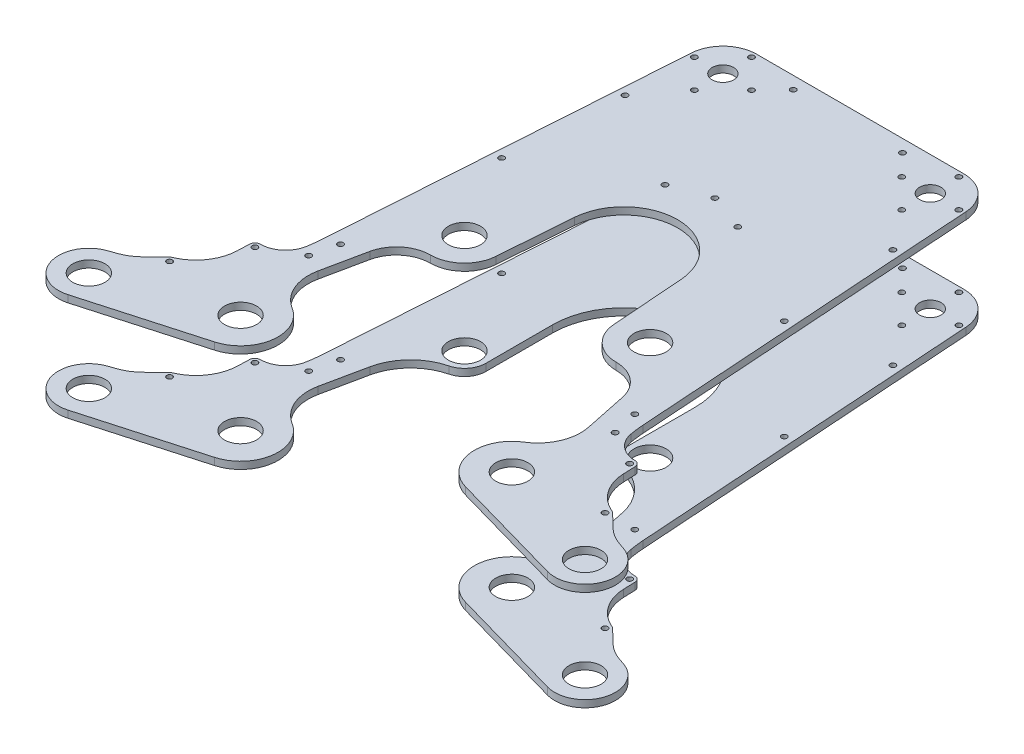
SolidWorks part; units mm, degrees
ref_plane "Alzado" through (0, 0, 0) normal (0, 0, 1) x (1, 0, 0)
ref_plane "Planta" through (0, 0, 0) normal (0, 1, 0) x (1, 0, 0)
ref_plane "Vista lateral" through (0, 0, 0) normal (1, 0, 0) x (0, 0, -1)
sketch "llantas" plane through (0, 0, 0) normal (0, 1, 0) x (1, 0, 0)
  line L0 (0, 221.5734) -> (0, 0) construction
  line L1 (-215.9, 0) -> (0, 0) construction
  circle A0 centre (-93.6625, 101.6) radius 50.8
  circle A1 centre (-215.9, 0) radius 38.1
  circle A2 centre (215.9, 0) radius 38.1
  circle A3 centre (93.6625, 101.6) radius 50.8
  dimension "D1" = 101.6
  dimension "D2" = 42.8625
  dimension "D3" = 177.8
  dimension "D4" = 76.2
  dimension "D5" = 101.6
sketch "cono" plane through (0, 0, 0) normal (1, 0, 0) x (0, 0, -1)
  line L0 (-76.2, 23.114) -> (-22.987, 324.358)
  line L1 (-22.987, 324.358) -> (22.987, 324.358)
  line L2 (0, 324.358) -> (0, 23.114) construction
  line L3 (76.2, 23.114) -> (-76.2, 23.114) construction
  line L4 (-76.2, 23.114) -> (-106.426, 23.114)
  line L5 (-106.426, 23.114) -> (-106.426, 0)
  line L6 (-106.426, 0) -> (106.426, 0)
  line L7 (0, 0) -> (0, 23.114)
  line L8 (-76.2, 23.114) -> (76.2, 23.114)
  line L9 (-80.283, 0) -> (80.283, 0)
  line L10 (221.5734, 0) -> (0, 0) construction
  line L11 (106.426, 23.114) -> (106.426, 0)
  line L12 (76.2, 23.114) -> (106.426, 23.114)
  line L13 (76.2, 23.114) -> (22.987, 324.358)
  line L14 (0, 220.8278) -> (41.275, 220.8278) construction
  dimension "D1" = 324.358
  dimension "D2" = 23.114
  dimension "D3" = 22.987
  dimension "D4" = 152.4
  dimension "D5" = 212.852
  dimension "D6" = 41.275
  dimension "D7" = 220.8278
sketch "Croquis4" plane through (0, 0, 0) normal (0, 1, 0) x (1, 0, 0)
  line L11 (0, 293.4478) -> (0, -300.8756) construction
  circle A36 centre (0, 179.087) radius 32.258
  dimension "D4" = 64.516
ref_plane "Plano1" through (0, 184.15, 0) normal (0, 1, 0) x (1, 0, 0)
sketch "Croquis11" plane through (0, 184.15, 0) normal (0, 1, 0) x (1, 0, 0)
  line L0 (0, -106.426) -> (0, 106.426) construction
  line L1 (-101.7784, 180.6897) -> (-111.1757, -58.1023) construction
  line L2 (0, 0) -> (0, -47.7539) construction
  line L3 (-82.7561, 181.459) -> (-54.1087, -55.7947) construction
  line L4 (-102.0644, -224.6803) -> (-63.9644, -63.6256) construction
  line L5 (-139.2356, -215.8869) -> (-101.1356, -54.8321) construction
  line L6 (0, 0) -> (-82.55, -59.2289) construction
  line L7 (0, 0) -> (0, -106.426) construction
  line L14 (-126.947, -202.253) -> (-226.9506, -237.178) construction
  line L15 (-114.353, -238.3143) -> (-214.3566, -273.2393) construction
  line L16 (0, 293.4478) -> (0, -300.8756) construction
  line L17 (-220.6536, -283.7836) -> (-120.65, -283.7836) construction
  circle A0 centre (0, 0) radius 47.7539 construction
  circle A1 centre (-82.55, -59.2289) radius 50.8
  circle A2 centre (-92.2365, 180.3142) radius 30
  arc A3 (-82.7561, 181.459) -> (-101.7784, 180.6897) centre (-92.2365, 180.3142) ccw construction
  arc A4 (-111.1757, -58.1023) -> (-54.1087, -55.7947) centre (-82.55, -59.2289) ccw construction
  arc A6 (-139.2356, -215.8869) -> (-102.0644, -224.6803) centre (-120.65, -220.2836) ccw construction
  arc A7 (-63.9644, -63.6256) -> (-101.1356, -54.8321) centre (-82.55, -59.2289) ccw construction
  circle A12 centre (-120.65, -220.2836) radius 50.8
  circle A13 centre (-220.6536, -255.2086) radius 28.575
  arc A14 (-226.9506, -237.178) -> (-214.3566, -273.2393) centre (-220.6536, -255.2086) ccw construction
  arc A15 (-114.353, -238.3143) -> (-139.2356, -215.8869) centre (-120.65, -220.2836) ccw construction
  dimension "D1" = 101.6
  dimension "D4" = 60
  dimension "D5" = 19.0986
  dimension "D6" = 57.2958
  dimension "D10" = 38.1972
  dimension "D17" = 101.6
  dimension "D13" = 57.15
  dimension "D14" = 38.1972
  dimension "D2" = 101.6
  dimension "D3" = 165.1
  dimension "D8" = 69.85
  dimension "D9" = 12.7
  dimension "D12" = 239.5431
sketch "Croquis40" plane through (0, 184.15, 0) normal (0, 1, 0) x (1, 0, 0)
  line L0 (-117.475, -110.0289) -> (117.475, -110.0289) construction
  line L1 (-117.475, -110.0289) -> (-117.475, -344.9789) construction
  line L2 (117.475, -110.0289) -> (117.475, -344.9789) construction
  line L3 (-117.475, -344.9789) -> (117.475, -344.9789) construction
  line L4 (0, 0) -> (0, -110.0289)
  circle A1 centre (-82.55, -59.2289) radius 50.8 construction
  dimension "D1" = 234.95
ref_plane "Plano2" through (0, 95.25, 0) normal (0, 1, 0) x (1, 0, 0)
sketch "Croquis12" plane through (0, 95.25, 0) normal (0, 1, 0) x (1, 0, 0)
  line L0 (0, 0) -> (0, -63.4576) construction
  circle A0 centre (0, 0) radius 63.4576 construction
  circle A1 centre (-82.55, -59.2289) radius 50.8
  circle A2 centre (-82.55, -59.2289) radius 50.8 construction
sketch "Croquis42" plane through (0, 184.15, 0) normal (0, 1, 0) x (1, 0, 0)
  line L10 (142.9479, -125.9298) -> (122.1686, 182.3319)
  line L11 (-47.6217, 3.5515) -> (-52.471, -61.4721)
  line L12 (-112.3836, -113.6275) -> (-120.3575, -151.7275)
  line L13 (-120.65, -220.2836) -> (-220.6536, -255.2086) construction
  line L14 (-111.5648, -252.3593) -> (-213.299, -281.1746)
  line L15 (0, 226.6032) -> (0, -226.6032) construction
  line L17 (229.5516, -229.7302) -> (219.3033, -226.1511)
  line L18 (-229.5516, -229.7302) -> (-219.3033, -226.1511)
  line L19 (-142.9479, -125.9298) -> (-122.1686, 182.3319)
  line L20 (-126.947, -202.253) -> (-226.9506, -237.178) construction
  line L21 (-92.2365, 210.3142) -> (92.2365, 210.3142)
  line L22 (111.5648, -252.3593) -> (213.299, -281.1746)
  line L23 (112.3836, -113.6275) -> (120.3575, -151.7275)
  line L24 (47.6217, 3.5515) -> (52.471, -61.4721)
  circle A11 centre (-220.6536, -255.2086) radius 14.2875
  circle A17 centre (-120.65, -220.2836) radius 14.2875
  circle A18 centre (-82.55, -59.2289) radius 14.2875
  arc A20 (47.6217, 3.5515) -> (-47.6217, 3.5515) centre (0, 0) ccw
  circle A21 centre (92.2365, 180.3142) radius 25.4 construction
  circle A22 centre (0, 0) radius 47.7539 construction
  arc A23 (-82.55, -89.3914) -> (-52.471, -61.4721) centre (-82.55, -59.2289) ccw
  arc A24 (-82.55, -89.3914) -> (-112.3836, -113.6275) centre (-82.55, -119.8714) ccw
  arc A25 (-111.5648, -252.3593) -> (-103.1106, -191.933) centre (-120.65, -220.2836) ccw
  arc A26 (-120.3575, -151.7275) -> (-103.1106, -191.933) centre (-83.0655, -159.5323) ccw
  arc A28 (-229.5516, -229.7302) -> (-213.299, -281.1746) centre (-220.6536, -255.2086) ccw
  circle A29 centre (120.65, -220.2836) radius 33.3375 construction
  circle A30 centre (117.6365, 180.3142) radius 2.4892
  circle A31 centre (-92.2365, 180.3142) radius 30 construction
  arc A32 (-92.2365, 210.3142) -> (-122.1686, 182.3319) centre (-92.2365, 180.3142) ccw
  circle A33 centre (-120.65, -220.2836) radius 33.3375 construction
  circle A34 centre (-92.2365, 180.3142) radius 25.4 construction
  circle A35 centre (-92.2365, 205.7142) radius 2.4892
  circle A36 centre (-66.8365, 180.3142) radius 2.4892
  circle A37 centre (-92.2365, 154.9142) radius 2.4892
  circle A38 centre (-117.6365, 180.3142) radius 2.4892
  circle A39 centre (92.2365, 154.9142) radius 2.4892
  circle A40 centre (66.8365, 180.3142) radius 2.4892
  circle A41 centre (92.2365, 205.7142) radius 2.4892
  arc A42 (92.2365, 210.3142) -> (122.1686, 182.3319) centre (92.2365, 180.3142) cw
  arc A43 (229.5516, -229.7302) -> (213.299, -281.1746) centre (220.6536, -255.2086) cw
  arc A44 (120.3575, -151.7275) -> (103.1106, -191.933) centre (83.0655, -159.5323) cw
  arc A45 (111.5648, -252.3593) -> (103.1106, -191.933) centre (120.65, -220.2836) cw
  arc A46 (82.55, -89.3914) -> (112.3836, -113.6275) centre (82.55, -119.8714) cw
  arc A47 (82.55, -89.3914) -> (52.471, -61.4721) centre (82.55, -59.2289) cw
  circle A48 centre (82.55, -59.2289) radius 14.2875
  circle A49 centre (120.65, -220.2836) radius 14.2875
  circle A50 centre (220.6536, -255.2086) radius 14.2875
  arc A52 (142.9479, -125.9298) -> (219.3033, -226.1511) centre (256.9891, -118.2425) ccw
  arc A53 (-219.3033, -226.1511) -> (-142.9479, -125.9298) centre (-256.9891, -118.2425) ccw
  circle A54 centre (-92.2365, 180.3142) radius 9.5631
  circle A55 centre (92.2365, 180.3142) radius 9.5631
  point P18 (-170.6518, -237.7461)
  point P52 (-92.2365, 180.3142)
  point P66 (148.0256, -201.2583)
  point P83 (0, 210.3142)
  point P85 (92.2365, 180.3142)
  point P86 (170.6518, -237.7461)
  point P90 (-148.0256, -201.2583)
  dimension "D1" = 28.575
  dimension "D2" = 19.05
  dimension "D3" = 12.7
  dimension "D4" = 15.875
  dimension "D5" = 38.1
  dimension "D7" = 30.48
  dimension "D8" = 50.8
  dimension "D9" = 4.9784
  dimension "D11" = 114.3
  dimension "D12" = 19.1262
  dimension "D6" = 38.1
  dimension "D10" = 4
extrude "4400-23-P-0501" add sketch "Croquis42" along normal blind 6.35
sketch "Croquis44" plane through (0, 95.25, 0) normal (0, 1, 0) x (1, 0, 0)
  line L0 (92.2365, 210.3142) -> (-92.2365, 210.3142) construction
  line L1 (-122.1686, 182.3319) -> (-142.9479, -125.9298) construction
  line L2 (92.2365, 210.3142) -> (-92.2365, 210.3142)
  line L3 (-122.1686, 182.3319) -> (-142.9479, -125.9298)
  line L4 (142.9479, -125.9298) -> (122.1686, 182.3319) construction
  line L5 (229.5516, -229.7302) -> (219.3033, -226.1511) construction
  line L6 (111.5648, -252.3593) -> (213.299, -281.1746) construction
  line L7 (112.3836, -113.6275) -> (120.3575, -151.7275) construction
  line L10 (-120.3575, -151.7275) -> (-112.3836, -113.6275) construction
  line L11 (-213.299, -281.1746) -> (-111.5648, -252.3593) construction
  line L12 (-219.3033, -226.1511) -> (-229.5516, -229.7302) construction
  line L13 (142.9479, -125.9298) -> (122.1686, 182.3319)
  line L14 (229.5516, -229.7302) -> (219.3033, -226.1511)
  line L15 (111.5648, -252.3593) -> (213.299, -281.1746)
  line L16 (112.3836, -113.6275) -> (120.3575, -151.7275)
  line L19 (-120.3575, -151.7275) -> (-112.3836, -113.6275)
  line L20 (-213.299, -281.1746) -> (-111.5648, -252.3593)
  line L21 (-219.3033, -226.1511) -> (-229.5516, -229.7302)
  line L22 (-63.4576, -59.2289) -> (-63.4576, 0)
  line L23 (63.4576, -59.2289) -> (63.4576, 0)
  line L24 (0, 0) -> (0, -147.841) construction
  arc A0 (-219.3033, -226.1511) -> (-142.9479, -125.9298) centre (-256.9891, -118.2425) ccw construction
  arc A1 (-92.2365, 210.3142) -> (-122.1686, 182.3319) centre (-92.2365, 180.3142) ccw construction
  arc A2 (-219.3033, -226.1511) -> (-142.9479, -125.9298) centre (-256.9891, -118.2425) ccw
  arc A3 (-92.2365, 210.3142) -> (-122.1686, 182.3319) centre (-92.2365, 180.3142) ccw
  arc A4 (122.1686, 182.3319) -> (92.2365, 210.3142) centre (92.2365, 180.3142) ccw construction
  arc A5 (142.9479, -125.9298) -> (219.3033, -226.1511) centre (256.9891, -118.2425) ccw construction
  arc A6 (213.299, -281.1746) -> (229.5516, -229.7302) centre (220.6536, -255.2086) ccw construction
  arc A7 (103.1106, -191.933) -> (111.5648, -252.3593) centre (120.65, -220.2836) ccw construction
  arc A8 (103.1106, -191.933) -> (120.3575, -151.7275) centre (83.0655, -159.5323) ccw construction
  arc A14 (-120.3575, -151.7275) -> (-103.1106, -191.933) centre (-83.0655, -159.5323) ccw construction
  arc A15 (-111.5648, -252.3593) -> (-103.1106, -191.933) centre (-120.65, -220.2836) ccw construction
  arc A16 (-229.5516, -229.7302) -> (-213.299, -281.1746) centre (-220.6536, -255.2086) ccw construction
  arc A17 (122.1686, 182.3319) -> (92.2365, 210.3142) centre (92.2365, 180.3142) ccw
  arc A18 (142.9479, -125.9298) -> (219.3033, -226.1511) centre (256.9891, -118.2425) ccw
  arc A19 (213.299, -281.1746) -> (229.5516, -229.7302) centre (220.6536, -255.2086) ccw
  arc A20 (103.1106, -191.933) -> (111.5648, -252.3593) centre (120.65, -220.2836) ccw
  arc A21 (103.1106, -191.933) -> (120.3575, -151.7275) centre (83.0655, -159.5323) ccw
  arc A27 (-120.3575, -151.7275) -> (-103.1106, -191.933) centre (-83.0655, -159.5323) ccw
  arc A28 (-111.5648, -252.3593) -> (-103.1106, -191.933) centre (-120.65, -220.2836) ccw
  arc A29 (-229.5516, -229.7302) -> (-213.299, -281.1746) centre (-220.6536, -255.2086) ccw
  circle A30 centre (92.2365, 180.3142) radius 9.5631 construction
  circle A31 centre (92.2365, 154.9142) radius 2.4892 construction
  circle A32 centre (117.6365, 180.3142) radius 2.4892 construction
  circle A33 centre (92.2365, 205.7142) radius 2.4892 construction
  circle A34 centre (66.8365, 180.3142) radius 2.4892 construction
  circle A35 centre (-92.2365, 180.3142) radius 9.5631 construction
  circle A36 centre (-66.8365, 180.3142) radius 2.4892 construction
  circle A37 centre (-92.2365, 205.7142) radius 2.4892 construction
  circle A38 centre (-117.6365, 180.3142) radius 2.4892 construction
  circle A39 centre (-92.2365, 154.9142) radius 2.4892 construction
  circle A40 centre (220.6536, -255.2086) radius 14.2875 construction
  circle A41 centre (120.65, -220.2836) radius 14.2875 construction
  circle A42 centre (82.55, -59.2289) radius 14.2875 construction
  circle A43 centre (-82.55, -59.2289) radius 14.2875 construction
  circle A44 centre (-120.65, -220.2836) radius 14.2875 construction
  circle A45 centre (-220.6536, -255.2086) radius 14.2875 construction
  circle A46 centre (92.2365, 180.3142) radius 9.5631
  circle A47 centre (92.2365, 154.9142) radius 2.4892
  circle A48 centre (117.6365, 180.3142) radius 2.4892
  circle A49 centre (92.2365, 205.7142) radius 2.4892
  circle A50 centre (66.8365, 180.3142) radius 2.4892
  circle A51 centre (-92.2365, 180.3142) radius 9.5631
  circle A52 centre (-66.8365, 180.3142) radius 2.4892
  circle A53 centre (-92.2365, 205.7142) radius 2.4892
  circle A54 centre (-117.6365, 180.3142) radius 2.4892
  circle A55 centre (-92.2365, 154.9142) radius 2.4892
  circle A56 centre (220.6536, -255.2086) radius 14.2875
  circle A57 centre (120.65, -220.2836) radius 14.2875
  circle A58 centre (82.55, -59.2289) radius 14.2875
  circle A59 centre (-82.55, -59.2289) radius 14.2875
  circle A60 centre (-120.65, -220.2836) radius 14.2875
  circle A61 centre (-220.6536, -255.2086) radius 14.2875
  arc A62 (63.4576, 0) -> (-63.4576, 0) centre (0, 0) ccw
  arc A64 (-63.4576, -59.2289) -> (-77.9, -77.7463) centre (-82.55, -59.2289) cw
  arc A65 (-112.3836, -113.6275) -> (-77.9, -77.7463) centre (-66.477, -123.2353) cw
  circle A66 centre (0, 0) radius 63.4576 construction
  arc A67 (112.3836, -113.6275) -> (77.9, -77.7463) centre (66.477, -123.2353) ccw
  arc A68 (63.4576, -59.2289) -> (77.9, -77.7463) centre (82.55, -59.2289) ccw
extrude "4400-23-P-0502" add sketch "Croquis44" along normal blind 6.35
sketch "Croquis45" plane through (0, 95.25, 0) normal (0, -1, 0) x (1, 0, 0)
  line L7 (-126.947, 202.253) -> (-226.9506, 237.178) construction
  circle A0 centre (-189.6273, 213.7178) radius 4.7625 construction
  circle A1 centre (-189.6273, 213.7178) radius 2.4892
  circle A6 centre (-220.6536, 255.2086) radius 38.1
  circle A7 centre (-220.6536, 255.2086) radius 38.1 construction
  circle A9 centre (-120.65, 220.2836) radius 63.5
  circle A10 centre (-120.65, 220.2836) radius 63.5 construction
  dimension "D1" = 9.525
  dimension "D2" = 4.9784
  dimension "D5" = 5.08
  dimension "D3" = 9.525
  dimension "D4" = 12.7
sketch "Croquis46" plane through (0, 190.5, 0) normal (0, 1, 0) x (1, 0, 0)
  line L0 (-184.6841, -242.6467) -> (-180.5992, -241.2201) construction
  line L1 (-126.947, -202.253) -> (-226.9506, -237.178) construction
  line L2 (-220.6536, -255.2086) -> (-120.65, -220.2836) construction
  line L3 (-182.6417, -241.9334) -> (-193.6494, -210.4142) construction
  line L4 (-166.6601, -156.7836) -> (-120.65, -156.7836) construction
  line L5 (-215.2247, -224.639) -> (-196.9587, -206.9893)
  line L6 (-172.6356, -195.3721) -> (-195.6603, -206.0971)
  line L7 (-172.6356, -195.3721) -> (-171.4196, -161.3759)
  line L8 (0, 0) -> (0, -195.4432) construction
  line L9 (166.6601, -156.7836) -> (120.65, -156.7836) construction
  line L10 (182.6417, -241.9334) -> (193.6494, -210.4142) construction
  line L11 (220.6536, -255.2086) -> (120.65, -220.2836) construction
  line L12 (184.6841, -242.6467) -> (180.5992, -241.2201) construction
  line L13 (172.6356, -195.3721) -> (171.4196, -161.3759)
  line L14 (172.6356, -195.3721) -> (195.6603, -206.0971)
  line L15 (215.2247, -224.639) -> (196.9587, -206.9893)
  circle A0 centre (-220.6536, -255.2086) radius 38.1 construction
  circle A1 centre (-193.6494, -210.4142) radius 4.7625 construction
  circle A2 centre (-193.6494, -210.4142) radius 2.4892
  circle A3 centre (-166.6601, -161.5461) radius 4.7625 construction
  circle A4 centre (-166.6601, -161.5461) radius 2.4892
  arc A5 (-219.3033, -226.1511) -> (-142.9479, -125.9298) centre (-256.9891, -118.2425) ccw construction
  circle A6 centre (-120.65, -220.2836) radius 63.5 construction
  arc A7 (-196.9587, -206.9893) -> (-195.6603, -206.0971) centre (-193.6494, -210.4142) cw
  arc A8 (-171.4196, -161.3759) -> (-166.6601, -156.7836) centre (-166.6601, -161.5461) cw
  arc A9 (-166.6601, -156.7836) -> (-144.4349, -138.1433) centre (-166.6601, -134.2137) ccw
  arc A10 (-215.2247, -224.639) -> (-144.4349, -138.1433) centre (-256.9891, -118.2425) ccw
  circle A11 centre (166.6601, -161.5461) radius 4.7625 construction
  circle A12 centre (193.6494, -210.4142) radius 4.7625 construction
  arc A13 (215.2247, -224.639) -> (144.4349, -138.1433) centre (256.9891, -118.2425) cw
  arc A14 (166.6601, -156.7836) -> (144.4349, -138.1433) centre (166.6601, -134.2137) cw
  arc A15 (171.4196, -161.3759) -> (166.6601, -156.7836) centre (166.6601, -161.5461) ccw
  arc A16 (196.9587, -206.9893) -> (195.6603, -206.0971) centre (193.6494, -210.4142) ccw
  circle A17 centre (166.6601, -161.5461) radius 2.4892
  circle A18 centre (193.6494, -210.4142) radius 2.4892
  point P20 (-182.6417, -241.9334)
  arc M29 (219.3033, -226.1511) -> (142.9479, -125.9298) centre (256.9891, -118.2425) cw
  arc M35 (-142.9479, -125.9298) -> (-219.3033, -226.1511) centre (-256.9891, -118.2425) cw
  dimension "D1" = 4.9784
  dimension "D2" = 9.525
  dimension "D4" = 6.35
  dimension "D3" = 9.525
  dimension "D5" = 25.4
extrude "Saliente-Extruir2" add sketch "Croquis46" against normal up to surface (6.35 mm away) contours A9 A8 L7 A4 M35 | A7 L5 A2 L6 M35 | L13 A15 A14 A17 M29 | A18 L15 A16 L14 M29 region at (-162.2772, 190.5, 168.9624) region at (-205.7326, 190.5, 216.1858) region at (162.2772, 190.5, 168.9624) region at (183.9298, 190.5, 201.203) up to face at (0, 184.15, 101.9028)
fillet "Redondeo1" radius 38.1 2 edges at (-215.2247, 187.325, 224.639) (-172.6356, 187.325, 195.3721)
extrude "Saliente-Extruir3" add sketch "Croquis46<3>" against normal up to surface (95.25 mm away) from surface contours A9 A8 L7 A4 M35 | A7 L5 A2 L6 M35 | L13 A15 A14 A17 M29 | A18 L15 A16 L14 M29 region at (-162.2772, 190.5, 168.9624) region at (-205.7326, 190.5, 216.1858) region at (162.2772, 190.5, 168.9624) region at (183.9298, 190.5, 201.203) up to face at (0, 95.25, 100.1304) starting at face at (-120.65, 101.6, 234.5711)
sketch "Croquis46<3>" plane through (0, 190.5, 0) normal (0, 1, 0) x (1, 0, 0) same geometry as "Croquis46"
fillet "Redondeo2" radius 38.1 2 edges at (-215.2247, 98.425, 224.639) (-172.6356, 98.425, 195.3721)
fillet "Redondeo3" radius 38.1 2 edges at (215.2247, 187.325, 224.639) (172.6356, 187.325, 195.3721)
fillet "Redondeo4" radius 38.1 2 edges at (215.2247, 98.425, 224.639) (172.6356, 98.425, 195.3721)
sketch "Croquis47" plane through (0, 190.5, 0) normal (0, 1, 0) x (1, 0, 0)
  line L0 (-139.2356, -215.8869) -> (-101.1356, -54.8321) construction
  line L4 (0, 0) -> (0, -211.1114) construction
  line L9 (-101.7784, 180.6897) -> (-111.1757, -58.1023) construction
  line L12 (92.2365, 210.3142) -> (-92.2365, 210.3142) construction
  line L14 (-82.7561, 181.459) -> (-54.1087, -55.7947) construction
  circle A0 centre (-136.2788, -144.0836) radius 4.7625 construction
  circle A1 centre (-136.2788, -144.0836) radius 2.4892
  circle A2 centre (-130.8514, -121.1414) radius 4.7625 construction
  circle A3 centre (-130.8514, -121.1414) radius 2.4892
  circle A5 centre (-120.65, -220.2836) radius 63.5 construction
  circle A7 centre (-82.55, -59.2289) radius 50.8 construction
  circle A8 centre (130.8514, -121.1414) radius 2.4892
  circle A9 centre (130.8514, -121.1414) radius 4.7625 construction
  circle A10 centre (136.2788, -144.0836) radius 2.4892
  circle A11 centre (136.2788, -144.0836) radius 4.7625 construction
  circle A12 centre (-119.0948, 120.1517) radius 2.4892
  circle A13 centre (-119.0948, 120.1517) radius 4.7625 construction
  circle A14 centre (-125.6973, 16.9711) radius 2.4892
  circle A15 centre (-125.6973, 16.9711) radius 4.7625 construction
  circle A17 centre (-92.2365, 180.3142) radius 30 construction
  circle A18 centre (125.6973, 16.9711) radius 4.7625 construction
  circle A19 centre (125.6973, 16.9711) radius 2.4892
  circle A20 centre (119.0948, 120.1517) radius 4.7625 construction
  circle A21 centre (119.0948, 120.1517) radius 2.4892
  circle A22 centre (-48.584, 199.2017) radius 4.7625 construction
  circle A23 centre (-48.584, 199.2017) radius 2.4892
  circle A24 centre (48.584, 199.2017) radius 2.4892
  circle A25 centre (48.584, 199.2017) radius 4.7625 construction
  circle A26 centre (0, 80.9201) radius 4.7625 construction
  circle A27 centre (0, 80.9201) radius 2.4892
  circle A28 centre (-32.3905, 68.9263) radius 2.4892
  circle A29 centre (-32.3905, 68.9263) radius 4.7625 construction
  circle A31 centre (0, 0) radius 63.4576 construction
  circle A32 centre (32.3905, 68.9263) radius 2.4892
  circle A33 centre (32.3905, 68.9263) radius 4.7625 construction
  dimension "D1" = 4.9784
  dimension "D2" = 9.525
  dimension "D3" = 8.89
  dimension "D4" = 8.89
  dimension "D5" = 12.7
  dimension "D6" = 6.35
  dimension "D7" = 9.525
  dimension "D8" = 4.9784
  dimension "D9" = 12.7
  dimension "D10" = 10.16
  dimension "D11" = 25.4
  dimension "D12" = 25.4
  dimension "D13" = 4.9784
  dimension "D14" = 9.525
  dimension "D15" = 8.89
  dimension "D16" = 6.35
  dimension "D17" = 9.525
  dimension "D18" = 4.9784
  dimension "D19" = 12.7
  dimension "D20" = 65.3447
  dimension "D21" = 12.7
  dimension "D22" = 31.75
extrude "Cortar-Extruir1" cut sketch "Croquis47" against normal through all
equation "\"D5@Croquis11\"=12*5MM/PI"
equation "\"D6@Croquis11\"=36*5mm/pi"
equation "\"D7@Croquis11\"=(120*5mm)+1mm"
equation "\"D10@Croquis11\"=24*5mm/pi"
equation "\"D11@Croquis11\"=(90*5mm)+1mm"
equation "\"D14@Croquis11\"=24*5mm/pi"
equation "\"D15@Croquis11\"=(70*5mm)+1mm"
